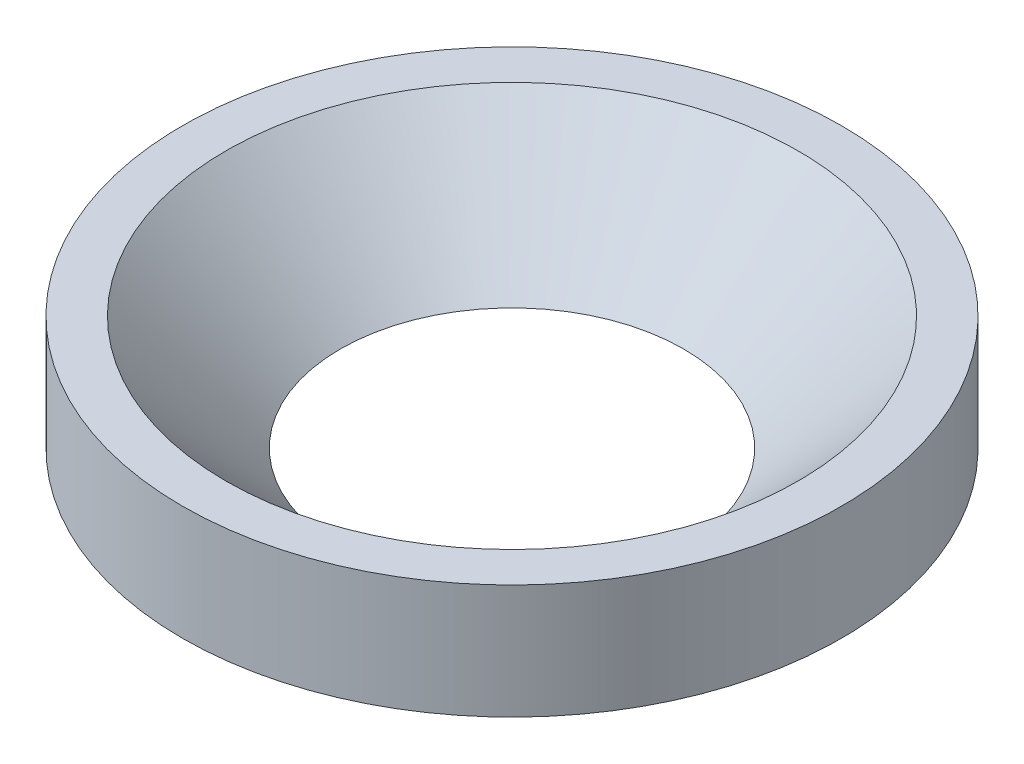
SolidWorks part; units mm, degrees
material "6061 Alloy"
ref_plane "Front Plane" through (0, 0, 0) normal (0, 0, 1) x (1, 0, 0)
ref_plane "Top Plane" through (0, 0, 0) normal (0, 1, 0) x (1, 0, 0)
ref_plane "Right Plane" through (0, 0, 0) normal (1, 0, 0) x (0, 0, -1)
sketch "Sketch1" plane through (0, 0, 0) normal (0, 1, 0) x (1, 0, 0)
  circle A0 centre (0, 0) radius 3
  circle A1 centre (0, 0) radius 5.76
  dimension "D1" = 6
  dimension "D2" = 11.52
extrude "Boss-Extrude1" add sketch "Sketch1" along normal blind 2
chamfer "Chamfer1" distance 2 1 edges at (0, 2, 3)
